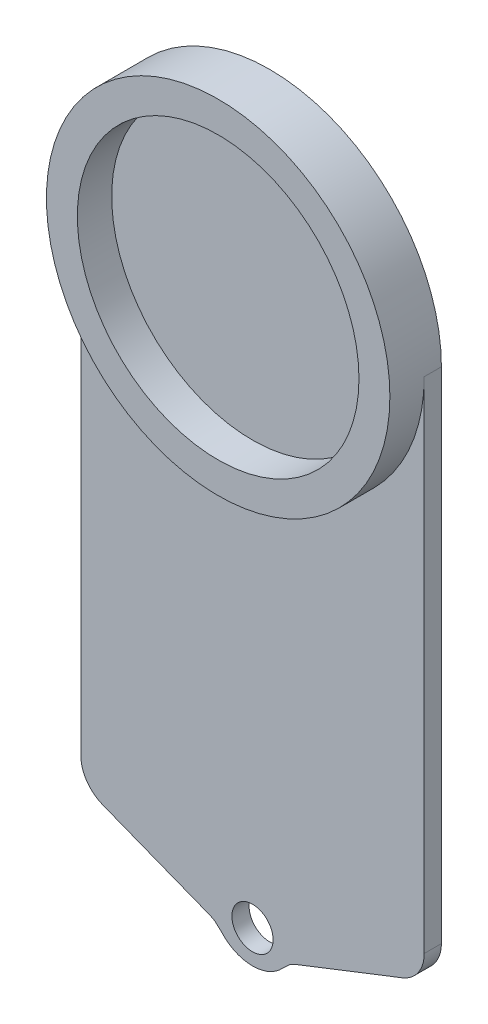
SolidWorks part; units mm, degrees
ref_plane "Alzado" through (0, 0, 0) normal (0, 0, 1) x (1, 0, 0)
ref_plane "Planta" through (0, 0, 0) normal (0, 1, 0) x (1, 0, 0)
ref_plane "Vista lateral" through (0, 0, 0) normal (1, 0, 0) x (0, 0, -1)
sketch "Croquis1" plane through (0, 0, 0) normal (0, 0, 1) x (1, 0, 0)
  line L12 (-50, 164) -> (-50, 11.7392)
  line L13 (13.7873, -2.4311) -> (20, 0)
  line L16 (-13.7873, -2.4311) -> (-20, 0)
  line L17 (-20, 0) -> (-50, 11.7392)
  line L18 (20, 0) -> (50, 11.7392)
  line L19 (50, 164) -> (50, 11.7392)
  circle A12 centre (0, 0) radius 6
  arc A15 (50, 164) -> (-50, 164) centre (0, 164) ccw
  arc A16 (-8.8548, -5.6773) -> (8.8548, -5.6773) centre (0, 2.4216) ccw
  spline S3 degree 3 poles (8.8548, -5.6773) (9.5176, -5.0903) (10.9007, -3.469) (12.7112, -2.8522) (13.7873, -2.4311) knots 0.517709 0.517709 0.517709 0.517709 0.741172 1 1 1 1
  spline S4 degree 3 poles (-8.8548, -5.6773) (-9.5176, -5.0903) (-10.9007, -3.469) (-12.7112, -2.8522) (-13.7873, -2.4311) knots 0.517709 0.517709 0.517709 0.517709 0.741172 1 1 1 1
  dimension "D1" = 12
  dimension "D6" = 100
  dimension "D3" = 20
  dimension "D4" = 164
extrude "Saliente-Extruir1" add sketch "Croquis1" along normal blind 5 contours L13 L18 L19 A15 L12 L17 L16 A12 region at (0, 103.1835, 0)
fillet "Redondeo1" radius 10 1 edges at (50, 11.7392, 2.5) type face fillet first side face at (50, 87.8696, 2.5) second side face at (31.8937, 4.6541, 2.5)
fillet "Redondeo3" radius 10 1 edges at (-50, 11.7392, 2.5)
sketch "Croquis2" plane through (0, 0, 5) normal (0, 0, 1) x (1, 0, 0)
  circle A0 centre (0, 164) radius 50
  circle A1 centre (0, 164) radius 41
  dimension "D1" = 100
  dimension "D2" = 82
extrude "Saliente-Extruir3" add sketch "Croquis2" along normal blind 10
